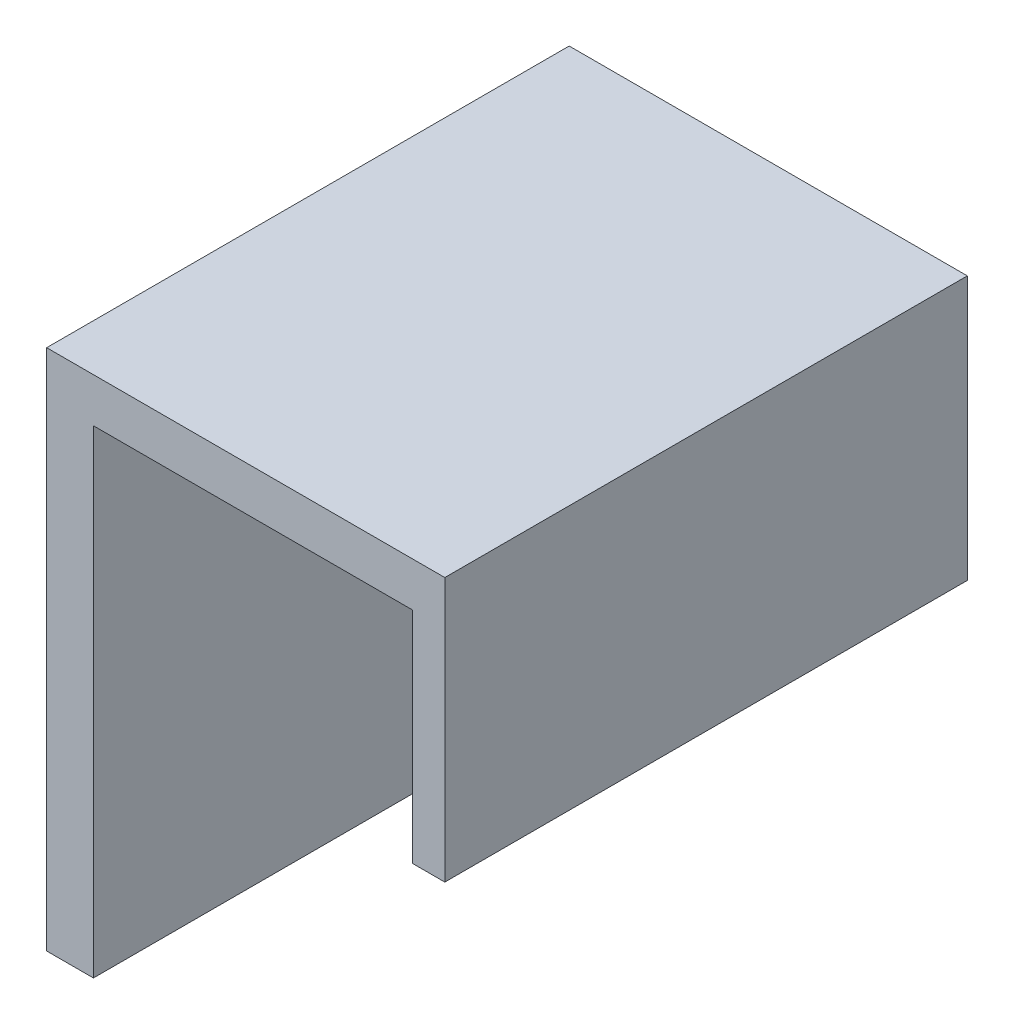
SolidWorks part; units mm, degrees
ref_plane "Front Plane" through (0, 0, 0) normal (0, 0, 1) x (1, 0, 0)
ref_plane "Top Plane" through (0, 0, 0) normal (0, 1, 0) x (1, 0, 0)
ref_plane "Right Plane" through (0, 0, 0) normal (1, 0, 0) x (0, 0, -1)
sketch "Sketch1" plane through (0, 0, 0) normal (0, 0, 1) x (1, 0, 0)
  line L0 (-2.5879, 20.4633) -> (-2.5879, -4.7444)
  line L1 (-2.5879, -4.7444) -> (1.1502, -4.7444)
  line L2 (1.1502, -4.7444) -> (1.1502, 25.5431)
  line L3 (1.1502, 25.5431) -> (-44.5687, 25.5431)
  line L4 (-44.5687, 25.5431) -> (-44.5687, -34.4569)
  line L5 (-44.5687, -34.4569) -> (-39.2013, -34.4569)
  line L6 (-39.2013, -34.4569) -> (-39.2013, 20.4633)
  line L7 (-39.2013, 20.4633) -> (-2.5879, 20.4633)
  dimension "D1" = 60
extrude "Boss-Extrude1" add sketch "Sketch1" along normal blind 60
